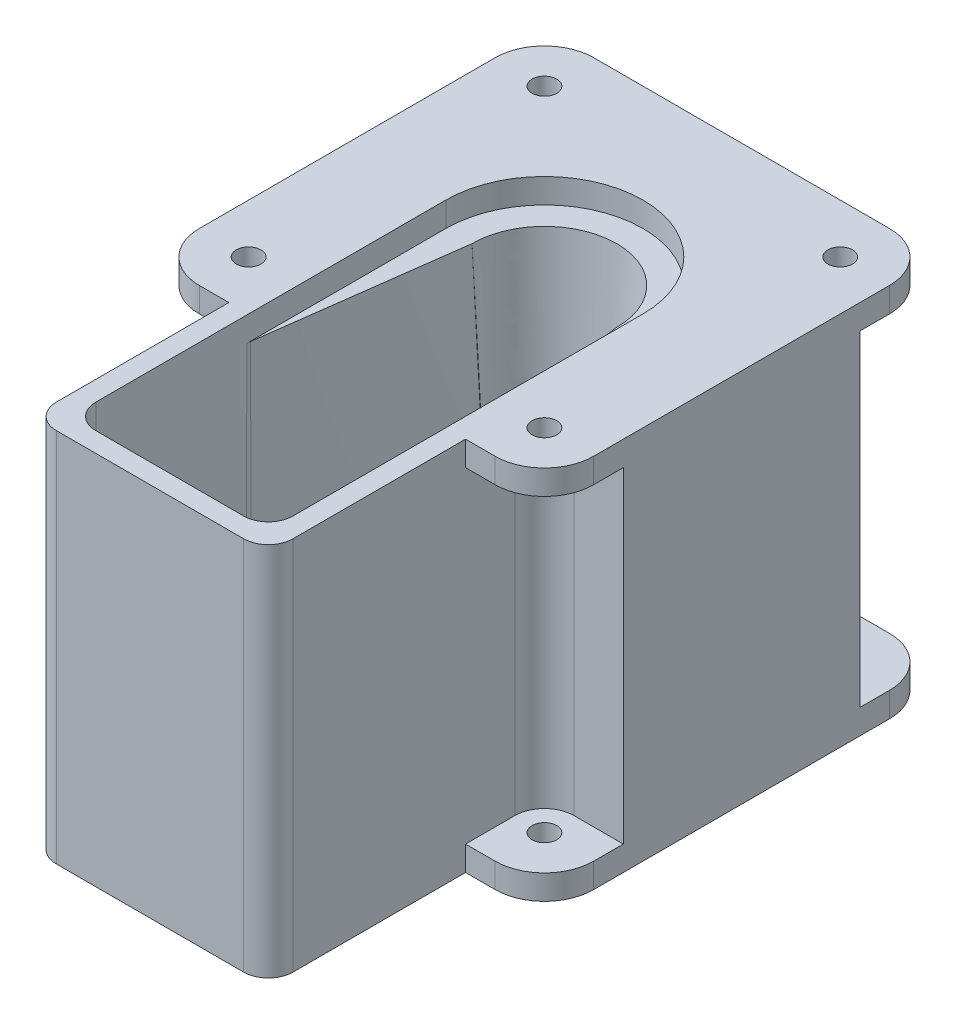
SolidWorks part; units mm, degrees
material "ABS"
ref_plane "Front Plane" through (0, 0, 0) normal (0, 0, 1) x (1, 0, 0)
ref_plane "Top Plane" through (0, 0, 0) normal (0, 1, 0) x (1, 0, 0)
ref_plane "Right Plane" through (0, 0, 0) normal (1, 0, 0) x (0, 0, -1)
sketch "Sketch1" plane through (0, 0, 0) normal (0, 1, 0) x (1, 0, 0)
  line L0 (40, 0) -> (-40, 0)
  line L1 (-40, -40) -> (40, -40)
  line L2 (-40, -40) -> (-40, 40)
  line L3 (-40, 40) -> (40, 40)
  line L4 (40, -40) -> (40, 40)
  line L5 (-40, -40) -> (40, 40) construction
  line L6 (-40, 40) -> (40, -40) construction
  point P0 (0, 0)
  dimension "D1" = 80
  dimension "D2" = 80
extrude "Boss-Extrude1" add sketch "Sketch1" along normal blind 76.125 contours L0 L4 L3 L2 region at (0, 0, -20)
sketch "Sketch2" plane through (0, 76.125, 0) normal (0, 1, 0) x (1, 0, 0)
  circle A0 centre (0, 0) radius 15
  dimension "D1" = 30
sketch "Sketch3" plane through (0, 0, 0) normal (0, -1, 0) x (1, 0, 0)
  line L0 (40, 0) -> (-40, 0) construction
  circle A0 centre (0, 0) radius 10.5
  dimension "D1" = 21
loft "Cut-Loft1" cut profiles "Sketch2", "Sketch3" connector at (-2.1975, 76.125, 14.8382) connector at (1.0801, 0, 10.4443)
fillet "Fillet1" radius 10 2 edges at (-40, 38.0625, -40) (40, 38.0625, -40)
ref_plane "Plane1" through (0, 5, 0) normal (0, -1, 0) x (-1, 0, 0)
sketch "Sketch4" plane through (0, 5, 0) normal (0, -1, 0) x (-1, 0, 0)
  line L8 (-40, 24) -> (-40, 30)
  line L10 (-24, 40) -> (-30, 40)
  line L11 (-30, 24) -> (-40, 24)
  line L12 (-24, 30) -> (-24, 40)
  arc A0 (-30, 40) -> (-40, 30) centre (-30, 30) ccw
  arc A4 (-30, 24) -> (-24, 30) centre (-30, 30) ccw
  dimension "D1" = 12
extrude "Cut-Extrude1" cut sketch "Sketch4" against normal offset from surface (66.125 mm away) 5 up to face at (5, 76.125, -18.0178)
sketch "Sketch5" plane through (0, 76.125, 0) normal (0, 1, 0) x (1, 0, 0)
  circle A0 centre (30, 30) radius 2.5
  circle A1 centre (-30, 30) radius 2.5
  dimension "D1" = 5
extrude "Cut-Extrude2" cut sketch "Sketch5" against normal through all
sketch "Sketch6" plane through (0, 76.125, 0) normal (0, 1, 0) x (1, 0, 0)
  circle A0 centre (0, 0) radius 20
  dimension "D1" = 40
extrude "Cut-Extrude3" cut sketch "Sketch6" against normal blind 5
mirror "Mirror1" about plane through (0, 0, 0) normal (1, 0, 0) of "Cut-Extrude1"
sketch "Sketch7" plane through (0, 76.125, 0) normal (0, 1, 0) x (1, 0, 0)
  line L1 (-20, 0) -> (-40, 0)
  line L2 (-20, 0) -> (-20, -40)
  line L3 (-20, -40) -> (-40, -40)
  line L4 (-40, 0) -> (-40, -40)
  line L6 (-40, 0) -> (-40, 30) construction
  line L8 (40, 0) -> (20, 0)
  line L9 (40, 0) -> (40, -40)
  line L10 (40, -40) -> (20, -40)
  line L11 (20, 0) -> (20, -40)
  dimension "D1" = 40
extrude "Boss-Extrude3" add sketch "Sketch7" against normal up to surface (76.125 mm away) up to face at (-30, 0, -27.5)
fillet "Fillet2" radius 10 2 edges at (-40, 38.0625, 40) (40, 38.0625, 40)
mirror "Mirror2" about plane through (0, 0, 0) normal (0, 0, 1) of "Cut-Extrude2", "Mirror1", "Cut-Extrude1"
sketch "Sketch8" plane through (0, 71.125, 0) normal (0, 1, 0) x (1, 0, 0)
  line L0 (14.684, 0) -> (20, -40)
  line L1 (20, -40) -> (20, 0)
  line L2 (20, 0) -> (14.684, 0)
sketch "Sketch9" plane through (0, 0, 0) normal (0, -1, 0) x (1, 0, 0)
  line L0 (20, 40) -> (20, 0)
  line L1 (20, 0) -> (10.5, 0)
  line L2 (10.5, 0) -> (20, 40)
loft "Loft1" add profiles "Sketch9", "Sketch8" connector at (10.5, 0, 0) connector at (14.684, 71.125, 0)
mirror "Mirror3" about plane through (0, 0, 0) normal (1, 0, 0) of "Loft1"
sketch "Sketch11" plane through (0, 0, 0) normal (1, 0, 0) x (0, 0, -1)
  line L0 (0, 0) -> (-40, 0)
  line L1 (-40, 0) -> (-40, 10)
  line L2 (-40, 71.125) -> (-40, 5) construction
  line L3 (0, 0) -> (0, 0.5)
  line L4 (0, 0.5) -> (-40, 10)
  dimension "D1" = 10
  dimension "D2" = 0.5
extrude "Boss-Extrude4" add sketch "Sketch11" along normal up to next and the other way up to next
sketch "Sketch12" plane through (0, 0, 0) normal (0, -1, 0) x (-1, 0, 0)
  circle A0 centre (0, 0) radius 10.5
extrude "Cut-Extrude4" cut sketch "Sketch12" against normal up to next
sketch "Sketch13" plane through (0, 0, 40) normal (0, 0, 1) x (1, 0, 0)
  line L0 (30, 0) -> (-30, 0) construction
  line L1 (-20, 76.125) -> (-24, 76.125)
  line L2 (-20, 76.125) -> (-20, 0)
  line L3 (-20, 0) -> (-24, 0)
  line L4 (-24, 76.125) -> (-24, 0)
  line L7 (-24, 71.125) -> (-24, 5) construction
extrude "Boss-Extrude5" add sketch "Sketch13" along normal blind 40
mirror "Mirror4" about plane through (0, 0, 0) normal (1, 0, 0) of "Boss-Extrude5"
sketch "Sketch14" plane through (-20, 0, 0) normal (1, 0, 0) x (0, 0, -1)
  line L0 (-40, 10) -> (-80, 19.5)
  line L1 (-80, 0) -> (-80, 76.125) construction
  line L2 (-80, 19.5) -> (-80, 0)
  line L3 (-80, 0) -> (-40, 0)
  line L4 (-80, 0) -> (-40, 0) construction
  line L5 (-40, 0) -> (-40, 10) construction
  line L6 (-40, 0) -> (-40, 10)
  line L7 (0, 0.5) -> (-40, 10) construction
extrude "Boss-Extrude6" add sketch "Sketch14" along normal up to next
sketch "Sketch15" plane through (0, 76.125, 0) normal (0, 1, 0) x (1, 0, 0)
  line L0 (20, 0) -> (20, -80) construction
  line L1 (-20, -80) -> (20, -80)
  line L2 (-20, -80) -> (-20, -76)
  line L3 (-20, -76) -> (20, -76)
  line L4 (20, -80) -> (20, -76)
  line L5 (-20, -80) -> (-24, -80) construction
extrude "Boss-Extrude7" add sketch "Sketch15" against normal up to next
fillet "Fillet3" radius 5 9 edges at (20, 47.3375, 76) (24, 38.0625, 80) (-24, 38.0625, 80) (-20, 47.3375, 76) (0, 18.55, 76)
